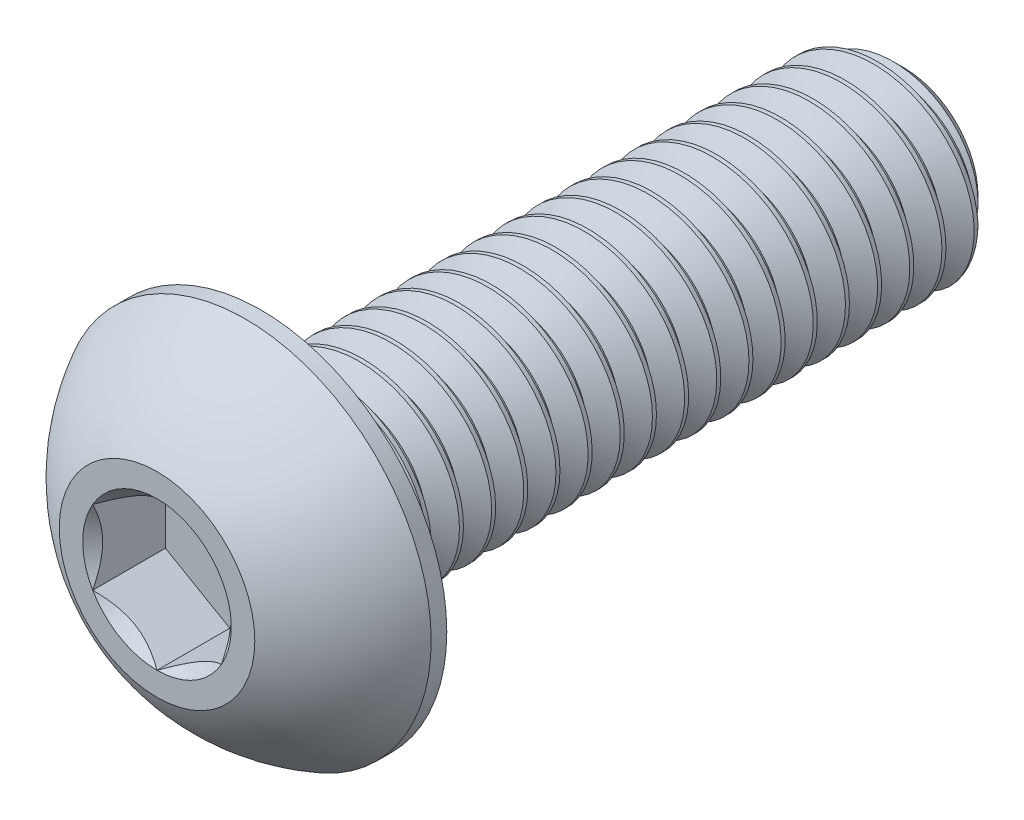
SolidWorks part; units mm, degrees
material "AISI 304"
ref_plane "Front" through (0, 0, 0) normal (0, 0, 1) x (1, 0, 0)
ref_plane "Top" through (0, 0, 0) normal (0, 1, 0) x (1, 0, 0)
ref_plane "Right" through (0, 0, 0) normal (1, 0, 0) x (0, 0, -1)
sketch "Sketch1" plane through (0, 0, 0) normal (1, 0, 0) x (0, 0, -1)
  line L2 (2.5654, 2.413) -> (18.4404, 2.413)
  line L3 (18.4404, 2.413) -> (18.4404, 0)
  line L4 (18.4404, 0) -> (2.5654, 0)
  line L6 (2.1806, 4.5847) -> (2.5654, 4.5847) construction
  line L7 (18.4404, 2.413) -> (18.4404, -2.413) construction
  line L8 (0, 0) -> (2.5654, 0) construction
  line L9 (2.5654, 4.5847) -> (2.5654, -4.5847) construction
  line L11 (2.5654, 2.413) -> (2.5654, 0)
  line L13 (0, 1.5875) -> (0, -1.5875) construction
  line L14 (0, 1.5875) -> (0, 2.413) construction
  arc A3 (0, 2.413) -> (2.1806, 4.5847) centre (4.5749, 0) cw construction
  dimension "D1" = 0.3848
revolve "Revolve1" add sketch "Sketch1" angle 360 mid plane about L4
sketch "Sketch3" plane through (0, 0, -18.4404) normal (0, 0, -1) x (-1, 0, 0)
  circle A0 centre (0, 0) radius 2.413
curve "Helix/Spiral1" pitch 0.7937 height 16.6687 turns 21
sketch "Sketch2" plane through (0, 0, 0) normal (1, 0, 0) x (0, 0, -1)
  line L0 (18.4404, 2.413) -> (19.1349, 2.413)
  line L1 (19.1349, 2.413) -> (18.8373, 1.8974)
  line L2 (18.8373, 1.8974) -> (18.7381, 1.8974)
  line L3 (18.7381, 1.8974) -> (18.4404, 2.413)
  line L4 (18.5892, 2.1552) -> (18.9861, 2.1552) construction
  dimension "D1" = 60
  dimension "D2" = 0.0992
  dimension "D3" = 0.3969
chamfer "Chamfer1" distance 0.5953 angle 45 1 edges at (0, 2.413, -18.4404)
sweep "Cut-Sweep1" cut profiles "Sketch2" path "Helix/Spiral1" align with end faces yes
sketch "Sketch7" plane through (0, 0, 0) normal (1, 0, 0) x (0, 0, -1)
  line L6 (2.1806, 4.5847) -> (2.5654, 4.5847) construction
  line L8 (0, 0) -> (2.5654, 0) construction
  line L11 (2.5654, 4.5847) -> (2.5654, -4.5847) construction
  line L12 (2.1806, 4.5847) -> (2.5654, 4.5847)
  line L13 (0, 0) -> (2.5654, 0)
  line L14 (0, 1.5875) -> (0, -1.5875) construction
  line L15 (2.5654, 4.5847) -> (2.5654, 0)
  line L16 (0, 2.413) -> (0, 0)
  arc A2 (2.1806, 4.5847) -> (0, 2.413) centre (4.5749, 0) ccw construction
  arc A3 (2.1806, 4.5847) -> (0, 2.413) centre (4.5749, 0) ccw
revolve "Revolve2" add sketch "Sketch7" angle 360 mid plane about L13
sketch "Sketch5" plane through (0, 0, 0) normal (0, 0, 1) x (1, 0, 0)
  line L1 (1.5875, -0.9165) -> (1.5875, 0.9165)
  line L2 (1.5875, 0.9165) -> (0, 1.8331)
  line L3 (0, 1.8331) -> (-1.5875, 0.9165)
  line L4 (-1.5875, 0.9165) -> (-1.5875, -0.9165)
  line L5 (-1.5875, -0.9165) -> (0, -1.8331)
  line L6 (0, -1.8331) -> (1.5875, -0.9165)
  circle A0 centre (0, 0) radius 1.5875 construction
extrude "Cut-Extrude2" cut sketch "Sketch5" against normal blind 1.7958
sketch "Sketch6" plane through (0, 0, 0) normal (0, 0, 1) x (1, 0, 0)
  circle A0 centre (0, 0) radius 1.8331
extrude "Cut-Extrude3" cut sketch "Sketch6" against normal blind 1.7958 draft 45
sketch "Sketch9" [suppressed] plane through (0, 0, -2.5654) normal (0, 0, 1) x (1, 0, 0)
  circle A2 centre (0, 0) radius 2.413
extrude "Boss-Extrude2" [suppressed] add sketch "Sketch9" against normal offset from surface (9.525 mm away) 31.75
sketch "Sketch10" plane through (0, 0, 0) normal (1, 0, 0) x (0, 0, -1)
  line L0 (18.4404, 2.413) -> (18.4404, -2.413) construction
  point P0 (17.2498, -2.413)
  dimension "D1" = 1.1906
equation "\"D3@Helix/Spiral1\" = \"Lg@Sketch1\" + \"D4@Helix/Spiral1\""
equation "\"D2@Sketch2\" = \"D4@Helix/Spiral1\" * .125"
equation "\"D3@Sketch2\" = \"D4@Helix/Spiral1\" * .5"
equation "\"D1@Chamfer1\" = \"D4@Helix/Spiral1\" * .75"
equation "\"D1@Cut-Extrude2\" = \"Head Ht@Sketch1\" * .7"
equation "\"D1@Sketch1\" = \"Head Ht@Sketch1\" * .15"
equation "\"D1@Sketch10\" = \"D4@Helix/Spiral1\" * 1.5"
equation "\"D1@Cut-Extrude3\" = \"D1@Cut-Extrude2\""
